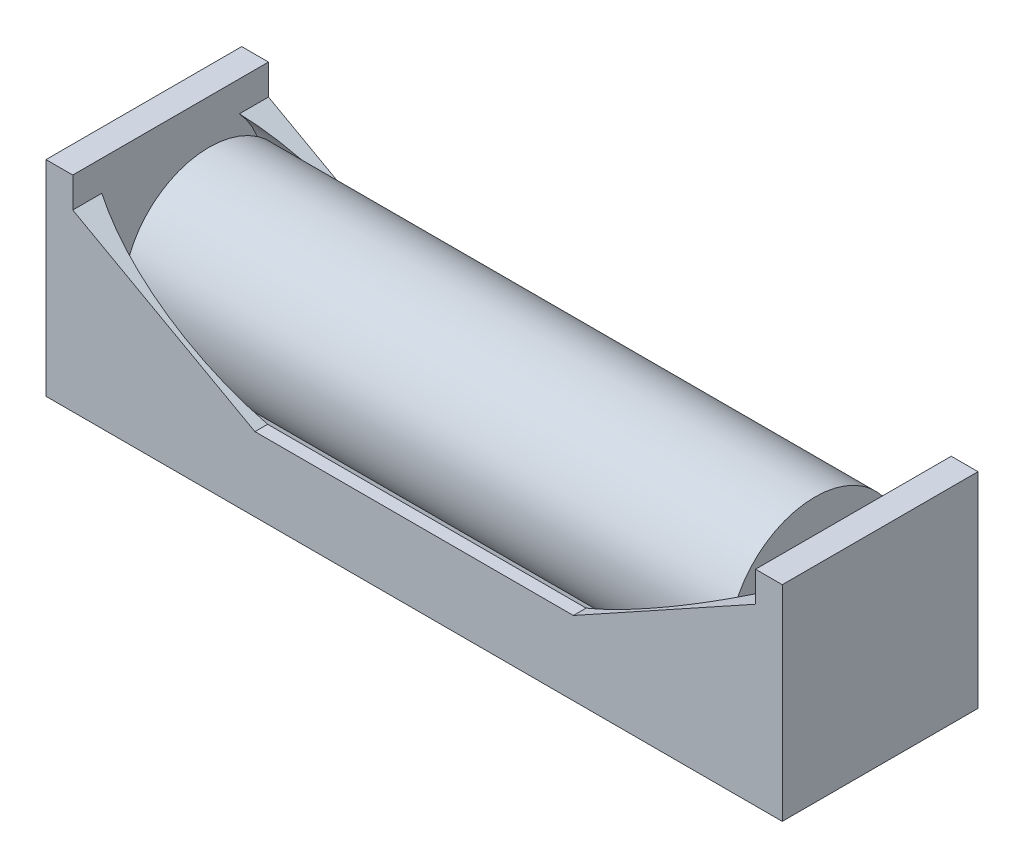
SolidWorks part; units mm, degrees
ref_plane "Front Plane" through (0, 0, 0) normal (0, 0, 1) x (1, 0, 0)
ref_plane "Top Plane" through (0, 0, 0) normal (0, 1, 0) x (1, 0, 0)
ref_plane "Right Plane" through (0, 0, 0) normal (1, 0, 0) x (0, 0, -1)
sketch "Sketch8" plane through (0, 0, 0) normal (1, 0, 0) x (0, 0, -1)
  line L0 (55, 0) -> (-55, 0) construction
  line L1 (0, 55) -> (0, -55) construction
  circle A0 centre (0, 9.2) radius 9.2
  dimension "D1" = 18.4
extrude "Boss-Extrude3" add sketch "Sketch8" along normal blind 32.5 and the other way blind 32.5
ref_plane "Plane1" through (0, -3, 0) normal (0, 1, 0) x (1, 0, 0)
sketch "Sketch9" plane through (0, -3, 0) normal (0, 1, 0) x (1, 0, 0)
  line L1 (-39.5, -10.5) -> (39.5, -10.5)
  line L2 (-39.5, -10.5) -> (-39.5, 10.5)
  line L3 (-39.5, 10.5) -> (39.5, 10.5)
  line L4 (39.5, -10.5) -> (39.5, 10.5)
  line L5 (-39.5, -10.5) -> (39.5, 10.5) construction
  line L6 (-39.5, 10.5) -> (39.5, -10.5) construction
  point P0 (0, 0)
  dimension "D1" = 79
  dimension "D2" = 21
extrude "Boss-Extrude4" add sketch "Sketch9" along normal blind 22 separate body
sketch "Sketch11" plane through (0, 0, 10.5) normal (0, 0, 1) x (1, 0, 0)
  line L0 (0, 0) -> (0, 50000) construction
  line L1 (-36.629, 19) -> (-36.629, 15.7468)
  line L2 (-39.5, 19) -> (39.5, 19) construction
  line L3 (-36.629, 15.7468) -> (-17.0836, 4.9297)
  line L4 (-17.0836, 4.9297) -> (0, 4.9297)
  line L5 (0, 4.9297) -> (0, 19)
  line L6 (0, 19) -> (-36.629, 19)
extrude "Cut-Extrude1" cut sketch "Sketch11" against normal through all
mirror "Mirror1" about plane through (0, 0, 0) normal (1, 0, 0) of "Cut-Extrude1"
sketch "Sketch12" plane through (-36.629, 0, 0) normal (1, 0, 0) x (0, 0, -1)
  line L0 (0, 0) -> (0, 50000) construction
  line L1 (-10.5, 19) -> (10.5, 19) construction
  circle A0 centre (0, 9) radius 10
  dimension "D1" = 20
extrude "Cut-Extrude2" cut sketch "Sketch12" along normal up to surface (73.258 mm away) up to face at (36.629, 17.3734, 0)
